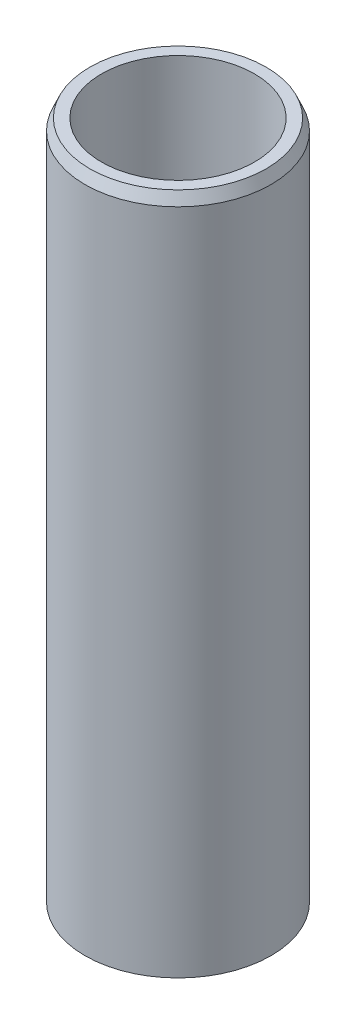
SolidWorks part; units mm, degrees
ref_plane "Front Plane" through (0, 0, 0) normal (0, 0, 1) x (1, 0, 0)
ref_plane "Top Plane" through (0, 0, 0) normal (0, 1, 0) x (1, 0, 0)
ref_plane "Right Plane" through (0, 0, 0) normal (1, 0, 0) x (0, 0, -1)
sketch "Sketch1" plane through (0, 0, 0) normal (0, 1, 0) x (1, 0, 0)
  circle A0 centre (0, 0) radius 40
  dimension "SHAFT_OD" = 80
extrude "Boss-Extrude1" add sketch "Sketch1" along normal blind 294.175
sketch "Sketch2" plane through (0, 0, 0) normal (0, 1, 0) x (1, 0, 0)
  circle A0 centre (0, 0) radius 32.8998
  dimension "BORE_D" = 65.7997
extrude "Cut-Extrude1" cut sketch "Sketch2" along normal through all
chamfer "Chamfer1" distance 4.8266 angle 23.458 2 edges at (0, 294.175, 40) (0, 0, 40) first distance on face at (0, 294.175, 40) first distance on face at (0, 0, 32.8998)
